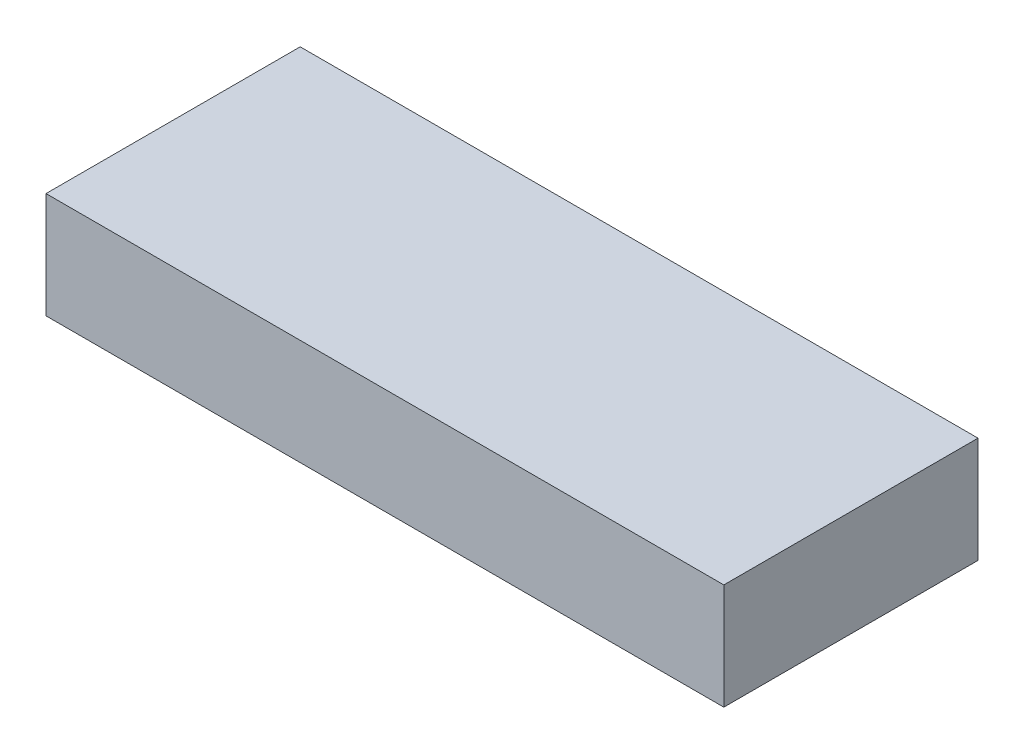
SolidWorks part; units mm, degrees
other "platform_body"
ref_plane "Front Plane" through (0, 0, 0) normal (0, 0, 1) x (1, 0, 0)
ref_plane "Top Plane" through (0, 0, 0) normal (0, 1, 0) x (1, 0, 0)
ref_plane "Right Plane" through (0, 0, 0) normal (1, 0, 0) x (0, 0, -1)
sketch "Sketch: Parent Structure" plane through (0, 0, 0) normal (0, 1, 0) x (1, 0, 0)
  line L1 (0, -18) -> (96, -18)
  line L2 (0, -18) -> (0, 18)
  line L3 (0, 18) -> (96, 18)
  line L4 (96, -18) -> (96, 18)
extrude "Parent Structure" add sketch "Sketch: Parent Structure" against normal blind 15
